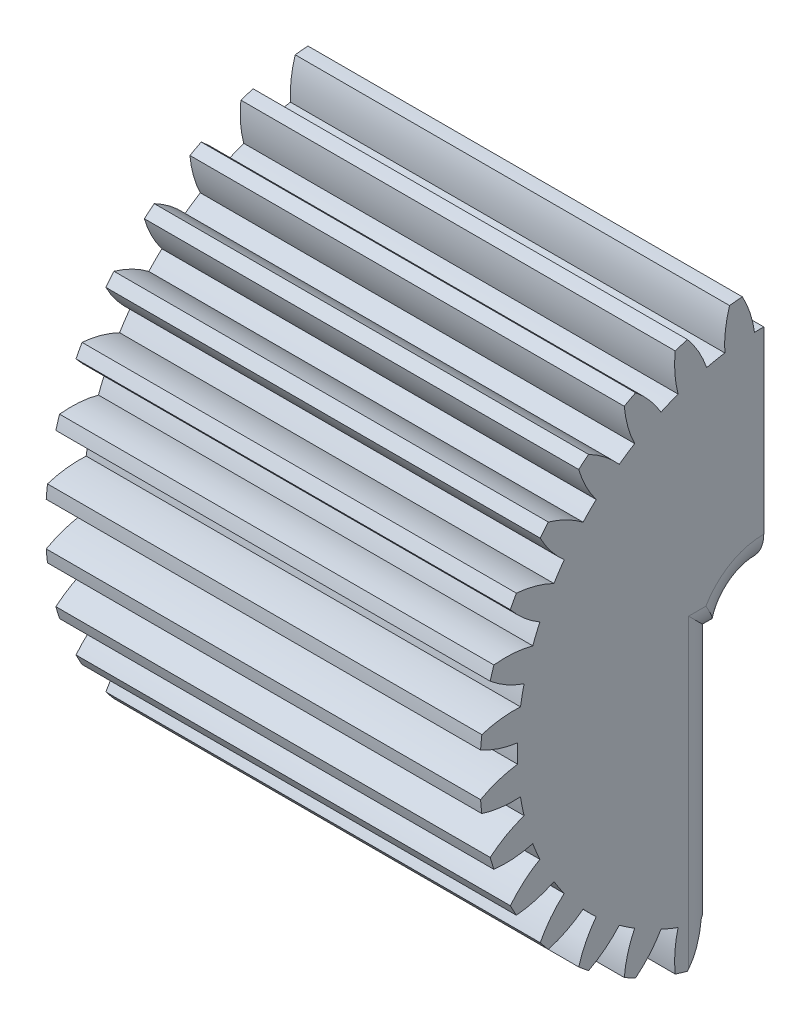
SolidWorks part; units mm, degrees
ref_plane "Plane1" through (0, 0, 0) normal (0, 0, 1) x (1, 0, 0)
ref_plane "Plane2" through (0, 0, 0) normal (0, 1, 0) x (1, 0, 0)
ref_plane "Plane3" through (0, 0, 0) normal (1, 0, 0) x (0, 0, -1)
other "Configuration Table"
sketch "HoldingSke" plane through (0, 0, 0) normal (0, 1, 0) x (1, 0, 0)
  line L0 (0, 0) -> (1.6961, -1.0598)
  line L1 (-15, 0) -> (100, 0) construction
  line L2 (0, 0) -> (-2.1039, 2.3779)
  line L3 (0, 0) -> (-11.863, 4.5341)
  line L4 (0, 0) -> (7.3237, 4.5764)
  line L5 (0, 0) -> (-46.8476, -17.4728)
  line L6 (0, 0) -> (-8.2896, -5.593)
  line L7 (-2.1039, 2.3779) -> (8.6586, 51.2059)
  line L8 (-76.2, 54.61) -> (-75.9, 54.61)
  line L9 (-67.7845, 28.3722) -> (-49.3413, 33.142)
  line L10 (-76.2, 71.12) -> (104.1128, 71.12)
  line L11 (0, 0) -> (-10, 0)
  line L12 (-76.2, 101.6) -> (-76.181, 101.6)
  line L13 (24.9733, 27.94) -> (52.9518, 28.4284)
  line L14 (24.9733, 27.94) -> (24.9743, 27.94)
  line L15 (24.9733, 27.94) -> (100.4006, 29.5858)
  line L16 (-63.627, -0.5) -> (-12.827, -0.5)
  circle A0 centre (0, 0) radius 1
  circle A1 centre (0, 0) radius 7.374
  circle A2 centre (0, 0) radius 37.5
  circle A3 centre (0, 0) radius 1
  dimension "Num_teeth" = 32
  dimension "Pitch_radius" = 180.3128
  dimension "Width" = 10
  dimension "Thickness" = 10
sketch "BasProSke" plane through (0, 0, 0) normal (0, 1, 0) x (1, 0, 0)
  line L0 (-10, 0) -> (60, 0) construction
  line L1 (0, 0) -> (0, 8.5)
  line L2 (0, 0) -> (10, 0)
  line L3 (10, 0) -> (10, 8.5)
  line L4 (10, 8.5) -> (0, 8.5)
  dimension "Thickness" = 10
  dimension "Diameter" = 17
revolve "Base-Revolve" add sketch "BasProSke" angle 360 about L0
sketch "TooCutSke" plane through (0, 0, 0) normal (1, 0, 0) x (0, 0, -1)
  line L1 (0, 0) -> (0, 107) construction
  line L2 (0, 0) -> (-0.4258, 7.9887) construction
  line L3 (0, 0) -> (-1.5667, 15.9069) construction
  line L4 (-0.4258, 7.9887) -> (-0.7833, 7.9534) construction
  arc A0 (0.277, 7.3688) -> (-0.277, 7.3688) centre (0, 0) ccw
  arc A1 (0.6561, 8.5001) -> (-0.6561, 8.5001) centre (0, 0) ccw
  circle A2 centre (0, 0) radius 8 construction
  circle A3 centre (0, 0) radius 7.7452 construction
  arc A4 (-0.277, 7.3688) -> (-0.6561, 8.5001) centre (-3.4475, 6.9356) ccw
  arc A5 (0.6561, 8.5001) -> (0.277, 7.3688) centre (3.4475, 6.9356) ccw
extrude "ToothCut" cut sketch "TooCutSke" along normal through all
fillet "Breaks" [suppressed] radius 0.01 tangent propagation no
fillet "RootFillets" [suppressed] radius 0.126
pattern_circular "TeethCuts" count 32 every 11.25 about axis through (-10, 0, 0) along (1, 0, 0) of "ToothCut", "RootFillets", "Breaks"
sketch "HubNeaOneSke" plane through (0, 0, 0) normal (-1, 0, 0) x (0, 0, 1)
  circle A0 centre (0, 0) radius 7.374
  dimension "Diameter" = 14.748
extrude "HubNearOne" [suppressed] add sketch "HubNeaOneSke" along normal blind 40.0001
sketch "HubNeaBotSke" plane through (0, 0, 0) normal (-1, 0, 0) x (0, 0, 1)
  circle A0 centre (0, 0) radius 7.374
  dimension "Diameter" = 14.748
extrude "HubNearBoth" [suppressed] add sketch "HubNeaBotSke" along normal blind 20
ref_plane "FarPln" through (10, 0, 0) normal (1, 0, 0) x (0, 0, -1)
sketch "HubFarSke" plane through (10, 0, 0) normal (1, 0, 0) x (0, 0, -1)
  circle A0 centre (0, 0) radius 7.374
  dimension "Diameter" = 14.748
extrude "HubFar" [suppressed] add sketch "HubFarSke" along normal blind 20
sketch "BorSke" plane through (0, 0, 0) normal (1, 0, 0) x (0, 0, -1)
  circle A0 centre (0, 0) radius 1
  dimension "Diameter" = 2
extrude "Bore" cut sketch "BorSke" along normal mid plane 100.0001
sketch "KeySke" plane through (0, 0, 0) normal (1, 0, 0) x (0, 0, -1)
  line L0 (-0.4, 0) -> (-0.4, 1.3)
  line L1 (-0.4, 1.3) -> (0.4, 1.3)
  line L2 (0.4, 1.3) -> (0.4, 0)
  line L3 (0, 0) -> (0, 34) construction
  line L4 (-0.4, 0) -> (0.4, 0)
  dimension "Width" = 0.8
extrude "Keyway" [suppressed] cut sketch "KeySke" along normal mid plane 100.0001
pattern_circular "Keyway2" [suppressed] count 2 every 90 about axis through (-10, 0, 0) along (1, 0, 0) reverse direction yes
sketch "Sketch1" plane through (10, 0, 0) normal (1, 0, 0) x (0, 0, -1)
  line L1 (-1.1, 0) -> (1.1, 0)
  line L2 (-1.1, 0) -> (-1.1, -12)
  line L3 (-1.1, -12) -> (1.1, -12)
  line L4 (1.1, 0) -> (1.1, -12)
  circle A0 centre (0, 0) radius 1 construction
  dimension "D3" = 12
  dimension "D1" = 2.2
  dimension "D2" = 1.1
  dimension "D4" = 12
extrude "Cut-Extrude1" cut sketch "Sketch1" against normal through all
sketch "Sketch2" plane through (0, 0, 0) normal (0, 0, 1) x (1, 0, 0)
  line L3 (4.25, 0) -> (9.75, 0)
  arc A0 (9.75, 0) -> (4.25, 0) centre (7, 0) ccw
  dimension "D2" = 5.5
  dimension "D1" = 7
revolve "Cut-Revolve1" cut sketch "Sketch2" angle 360 about L3
ref_plane "Plane4" through (3, 0, 0) normal (-1, 0, 0) x (0, 0, 1)
sketch "Sketch4" plane through (3, 0, 0) normal (-1, 0, 0) x (0, 0, 1)
  circle A0 centre (0, 0) radius 1.125
  circle A1 centre (0, 0) radius 0.5
  dimension "D1" = 1
  dimension "D2" = 2.25
extrude "Boss-Extrude1" add sketch "Sketch4" along normal blind 0.5 and the other way blind 0.5
sketch "Sketch5" plane through (0, 0, -1.1) normal (0, 0, 1) x (1, 0, 0)
  line L0 (0, -8.1488) -> (10, -8.1488) construction
  line L1 (0, 0) -> (2.5, 0)
  line L2 (0, 0) -> (0, -8.1488)
  line L3 (0, -8.1488) -> (2.5, -8.1488)
  line L4 (2.5, 0) -> (2.5, -8.1488)
  dimension "D1" = 2.5
extrude "Boss-Extrude2" add sketch "Sketch5" along normal up to next
sketch "Sketch6" plane through (0, 0, 0) normal (-1, 0, 0) x (0, 0, 1)
  line L0 (1, 0) -> (-1, 0) construction
  circle A0 centre (0, 0) radius 2.25
  dimension "D1" = 4.5
extrude "Cut-Extrude4" cut sketch "Sketch6" against normal blind 2.45
sketch "Sketch7" plane through (2.5, 0, 0) normal (1, 0, 0) x (0, 0, -1)
  circle A0 centre (0, 0) radius 0.5
extrude "Cut-Extrude5" cut sketch "Sketch7" against normal blind 2.4
sketch "Sketch8" plane through (0, 0, 0) normal (0, 0, 1) x (1, 0, 0)
  line L0 (0, 0.277) -> (0, -0.277) construction
  line L1 (-0.5, 9) -> (10.5, 9)
  line L2 (-0.5, 9) -> (-0.5, -9)
  line L3 (-0.5, -9) -> (10.5, -9)
  line L4 (10.5, 9) -> (10.5, -9)
  point P6 (0, 0)
  dimension "D1" = 11
  dimension "D2" = 18
  dimension "D3" = 0.5
  dimension "D4" = 9
extrude "Cut-Extrude6" cut sketch "Sketch8" against normal blind 10
sketch "Sketch9" plane through (0, 0, 0) normal (0, 0, -1) x (-1, 0, 0)
  line L0 (-10, 1) -> (-10, 7.374) construction
  line L1 (-8.5, 5.75) -> (-6.5, 5.75)
  line L2 (-8.5, 5.75) -> (-8.5, 3.75)
  line L3 (-8.5, 3.75) -> (-6.5, 3.75)
  line L4 (-6.5, 5.75) -> (-6.5, 3.75)
  line L5 (-3.5, 5.75) -> (-1.5, 5.75)
  line L6 (-3.5, 5.75) -> (-3.5, 3.75)
  line L7 (-3.5, 3.75) -> (-1.5, 3.75)
  line L8 (-1.5, 5.75) -> (-1.5, 3.75)
  line L9 (0, -2.25) -> (0, 2.25) construction
  line L10 (0, 7.374) -> (0, 2.25) construction
  point P12 (0, 0)
  dimension "D1" = 2
  dimension "D2" = 2
  dimension "D3" = 2
  dimension "D4" = 2
  dimension "D5" = 1.5
  dimension "D6" = 3.75
  dimension "D7" = 3.75
  dimension "D8" = 1.5
extrude "Boss-Extrude3" add sketch "Sketch9" along normal blind 2
sketch "Sketch10" plane through (10, 0, 0) normal (1, 0, 0) x (0, 0, -1)
  line L1 (0, 0) -> (-1.25, 0)
  line L2 (0, 0) -> (0, -9)
  line L3 (0, -9) -> (-1.25, -9)
  line L4 (-1.25, 0) -> (-1.25, -9)
  dimension "D1" = 1.25
  dimension "D2" = 9
extrude "Cut-Extrude7" cut sketch "Sketch10" against normal blind 7
ref_plane "Plane5" through (12, 0, 0) normal (1, 0, 0) x (0, 0, -1)
sketch "Sketch11" plane through (12, 0, 0) normal (1, 0, 0) x (0, 0, -1)
  line L0 (-1.25, 0) -> (-1.25, -7.2673) construction
  line L1 (-1, 0) -> (-1.25, 0) construction
  line L2 (0, 1) -> (0, 7.374) construction
  line L3 (-1.25, 0) -> (-1.25, -7.2673)
  line L4 (-1, 0) -> (-1.25, 0)
  line L5 (0, 1) -> (0, 7.374)
  arc A0 (-2.2837, 8.1875) -> (-2.6499, 8.0764) centre (0, 0) ccw construction
  arc A1 (-0.6425, 8.4757) -> (-1.0233, 8.4382) centre (0, 0) ccw construction
  arc A2 (-1.1659, 7.2812) -> (-1.7093, 7.1732) centre (0, 0) ccw construction
  arc A3 (-3.8371, 7.5846) -> (-4.1746, 7.4042) centre (0, 0) ccw construction
  arc A4 (-2.564, 6.9139) -> (-3.0758, 6.7019) centre (0, 0) ccw construction
  arc A5 (-3.8636, 6.2808) -> (-4.3242, 5.973) centre (0, 0) ccw construction
  arc A6 (-5.2431, 6.6903) -> (-5.5389, 6.4475) centre (0, 0) ccw construction
  arc A7 (-5.0147, 5.4064) -> (-5.4064, 5.0147) centre (0, 0) ccw construction
  arc A8 (-6.4475, 5.5389) -> (-6.6903, 5.2431) centre (0, 0) ccw construction
  arc A9 (-7.4042, 4.1746) -> (-7.5846, 3.8371) centre (0, 0) ccw construction
  arc A10 (-5.973, 4.3242) -> (-6.2808, 3.8636) centre (0, 0) ccw construction
  arc A11 (-6.7019, 3.0758) -> (-6.9139, 2.564) centre (0, 0) ccw construction
  arc A12 (-8.0764, 2.6499) -> (-8.1875, 2.2837) centre (0, 0) ccw construction
  arc A13 (-7.1732, 1.7093) -> (-7.2812, 1.1659) centre (0, 0) ccw construction
  arc A14 (-8.4382, 1.0233) -> (-8.4757, 0.6425) centre (0, 0) ccw construction
  arc A15 (-7.3688, 0.277) -> (-7.3688, -0.277) centre (0, 0) ccw construction
  arc A16 (-8.4757, -0.6425) -> (-8.4382, -1.0233) centre (0, 0) ccw construction
  arc A17 (-7.2812, -1.1659) -> (-7.1732, -1.7093) centre (0, 0) ccw construction
  arc A18 (-8.1875, -2.2837) -> (-8.0764, -2.6499) centre (0, 0) ccw construction
  arc A19 (-6.9139, -2.564) -> (-6.7019, -3.0758) centre (0, 0) ccw construction
  arc A20 (-7.5846, -3.8371) -> (-7.4042, -4.1746) centre (0, 0) ccw construction
  arc A21 (-6.2808, -3.8636) -> (-5.973, -4.3242) centre (0, 0) ccw construction
  arc A22 (-6.6903, -5.2431) -> (-6.4475, -5.5389) centre (0, 0) ccw construction
  arc A23 (-5.4064, -5.0147) -> (-5.0147, -5.4064) centre (0, 0) ccw construction
  arc A24 (-5.5389, -6.4475) -> (-5.2431, -6.6903) centre (0, 0) ccw construction
  arc A25 (-4.3242, -5.973) -> (-3.8636, -6.2808) centre (0, 0) ccw construction
  arc A26 (-4.1746, -7.4042) -> (-3.8371, -7.5846) centre (0, 0) ccw construction
  arc A27 (-3.0758, -6.7019) -> (-2.564, -6.9139) centre (0, 0) ccw construction
  arc A28 (-1.7093, -7.1732) -> (-1.25, -7.2673) centre (0, 0) ccw construction
  arc A29 (-2.6499, -8.0764) -> (-2.2837, -8.1875) centre (0, 0) ccw construction
  arc A30 (-2.2837, -8.1875) -> (-1.7093, -7.1732) centre (-4.7344, -6.1297) ccw construction
  arc A31 (-2.564, -6.9139) -> (-2.6499, -8.0764) centre (0.531, -7.727) ccw construction
  arc A32 (-3.8371, -7.5846) -> (-3.0758, -6.7019) centre (-5.8392, -5.0883) ccw construction
  arc A33 (-3.8636, -6.2808) -> (-4.1746, -7.4042) centre (-0.9867, -7.6821) ccw construction
  arc A34 (-5.2431, -6.6903) -> (-4.3242, -5.973) centre (-6.7197, -3.8514) ccw construction
  arc A35 (-5.0147, -5.4064) -> (-5.5389, -6.4475) centre (-2.4664, -7.342) ccw construction
  arc A36 (-6.4475, -5.5389) -> (-5.4064, -5.0147) centre (-7.342, -2.4664) ccw construction
  arc A37 (-5.973, -4.3242) -> (-6.6903, -5.2431) centre (-3.8514, -6.7197) ccw construction
  arc A38 (-7.4042, -4.1746) -> (-6.2808, -3.8636) centre (-7.6821, -0.9867) ccw construction
  arc A39 (-6.7019, -3.0758) -> (-7.5846, -3.8371) centre (-5.0883, -5.8392) ccw construction
  arc A40 (-8.0764, -2.6499) -> (-6.9139, -2.564) centre (-7.727, 0.531) ccw construction
  arc A41 (-7.1732, -1.7093) -> (-8.1875, -2.2837) centre (-6.1297, -4.7344) ccw construction
  arc A42 (-8.4382, -1.0233) -> (-7.2812, -1.1659) centre (-7.4749, 2.0282) ccw construction
  arc A43 (-7.3688, -0.277) -> (-8.4757, -0.6425) centre (-6.9356, -3.4475) ccw construction
  arc A44 (-8.4757, 0.6425) -> (-7.3688, 0.277) centre (-6.9356, 3.4475) ccw construction
  arc A45 (-7.2812, 1.1659) -> (-8.4382, 1.0233) centre (-7.4749, -2.0282) ccw construction
  arc A46 (-8.1875, 2.2837) -> (-7.1732, 1.7093) centre (-6.1297, 4.7344) ccw construction
  arc A47 (-6.9139, 2.564) -> (-8.0764, 2.6499) centre (-7.727, -0.531) ccw construction
  arc A48 (-7.5846, 3.8371) -> (-6.7019, 3.0758) centre (-5.0883, 5.8392) ccw construction
  arc A49 (-6.2808, 3.8636) -> (-7.4042, 4.1746) centre (-7.6821, 0.9867) ccw construction
  arc A50 (-6.6903, 5.2431) -> (-5.973, 4.3242) centre (-3.8514, 6.7197) ccw construction
  arc A51 (-5.4064, 5.0147) -> (-6.4475, 5.5389) centre (-7.342, 2.4664) ccw construction
  arc A52 (-5.5389, 6.4475) -> (-5.0147, 5.4064) centre (-2.4664, 7.342) ccw construction
  arc A53 (-4.3242, 5.973) -> (-5.2431, 6.6903) centre (-6.7197, 3.8514) ccw construction
  arc A54 (-4.1746, 7.4042) -> (-3.8636, 6.2808) centre (-0.9867, 7.6821) ccw construction
  arc A55 (-3.0758, 6.7019) -> (-3.8371, 7.5846) centre (-5.8392, 5.0883) ccw construction
  arc A56 (-2.6499, 8.0764) -> (-2.564, 6.9139) centre (0.531, 7.727) ccw construction
  arc A57 (-1.7093, 7.1732) -> (-2.2837, 8.1875) centre (-4.7344, 6.1297) ccw construction
  arc A58 (-1.0233, 8.4382) -> (-1.1659, 7.2812) centre (2.0282, 7.4749) ccw construction
  arc A59 (-0.277, 7.3688) -> (-0.6425, 8.4757) centre (-3.4475, 6.9356) ccw construction
  arc A60 (0, 7.374) -> (-0.277, 7.3688) centre (0, 0) ccw construction
  arc A61 (0, 1) -> (-1, 0) centre (0, 0) ccw construction
  arc A62 (-2.2837, 8.1875) -> (-2.6499, 8.0764) centre (0, 0) ccw
  arc A63 (-0.6425, 8.4757) -> (-1.0233, 8.4382) centre (0, 0) ccw
  arc A64 (-1.1659, 7.2812) -> (-1.7093, 7.1732) centre (0, 0) ccw
  arc A65 (-3.8371, 7.5846) -> (-4.1746, 7.4042) centre (0, 0) ccw
  arc A66 (-2.564, 6.9139) -> (-3.0758, 6.7019) centre (0, 0) ccw
  arc A67 (-3.8636, 6.2808) -> (-4.3242, 5.973) centre (0, 0) ccw
  arc A68 (-5.2431, 6.6903) -> (-5.5389, 6.4475) centre (0, 0) ccw
  arc A69 (-5.0147, 5.4064) -> (-5.4064, 5.0147) centre (0, 0) ccw
  arc A70 (-6.4475, 5.5389) -> (-6.6903, 5.2431) centre (0, 0) ccw
  arc A71 (-7.4042, 4.1746) -> (-7.5846, 3.8371) centre (0, 0) ccw
  arc A72 (-5.973, 4.3242) -> (-6.2808, 3.8636) centre (0, 0) ccw
  arc A73 (-6.7019, 3.0758) -> (-6.9139, 2.564) centre (0, 0) ccw
  arc A74 (-8.0764, 2.6499) -> (-8.1875, 2.2837) centre (0, 0) ccw
  arc A75 (-7.1732, 1.7093) -> (-7.2812, 1.1659) centre (0, 0) ccw
  arc A76 (-8.4382, 1.0233) -> (-8.4757, 0.6425) centre (0, 0) ccw
  arc A77 (-7.3688, 0.277) -> (-7.3688, -0.277) centre (0, 0) ccw
  arc A78 (-8.4757, -0.6425) -> (-8.4382, -1.0233) centre (0, 0) ccw
  arc A79 (-7.2812, -1.1659) -> (-7.1732, -1.7093) centre (0, 0) ccw
  arc A80 (-8.1875, -2.2837) -> (-8.0764, -2.6499) centre (0, 0) ccw
  arc A81 (-6.9139, -2.564) -> (-6.7019, -3.0758) centre (0, 0) ccw
  arc A82 (-7.5846, -3.8371) -> (-7.4042, -4.1746) centre (0, 0) ccw
  arc A83 (-6.2808, -3.8636) -> (-5.973, -4.3242) centre (0, 0) ccw
  arc A84 (-6.6903, -5.2431) -> (-6.4475, -5.5389) centre (0, 0) ccw
  arc A85 (-5.4064, -5.0147) -> (-5.0147, -5.4064) centre (0, 0) ccw
  arc A86 (-5.5389, -6.4475) -> (-5.2431, -6.6903) centre (0, 0) ccw
  arc A87 (-4.3242, -5.973) -> (-3.8636, -6.2808) centre (0, 0) ccw
  arc A88 (-4.1746, -7.4042) -> (-3.8371, -7.5846) centre (0, 0) ccw
  arc A89 (-3.0758, -6.7019) -> (-2.564, -6.9139) centre (0, 0) ccw
  arc A90 (-1.7093, -7.1732) -> (-1.25, -7.2673) centre (0, 0) ccw
  arc A91 (-2.6499, -8.0764) -> (-2.2837, -8.1875) centre (0, 0) ccw
  arc A92 (-2.2837, -8.1875) -> (-1.7093, -7.1732) centre (-4.7344, -6.1297) ccw
  arc A93 (-2.564, -6.9139) -> (-2.6499, -8.0764) centre (0.531, -7.727) ccw
  arc A94 (-3.8371, -7.5846) -> (-3.0758, -6.7019) centre (-5.8392, -5.0883) ccw
  arc A95 (-3.8636, -6.2808) -> (-4.1746, -7.4042) centre (-0.9867, -7.6821) ccw
  arc A96 (-5.2431, -6.6903) -> (-4.3242, -5.973) centre (-6.7197, -3.8514) ccw
  arc A97 (-5.0147, -5.4064) -> (-5.5389, -6.4475) centre (-2.4664, -7.342) ccw
  arc A98 (-6.4475, -5.5389) -> (-5.4064, -5.0147) centre (-7.342, -2.4664) ccw
  arc A99 (-5.973, -4.3242) -> (-6.6903, -5.2431) centre (-3.8514, -6.7197) ccw
  arc A100 (-7.4042, -4.1746) -> (-6.2808, -3.8636) centre (-7.6821, -0.9867) ccw
  arc A101 (-6.7019, -3.0758) -> (-7.5846, -3.8371) centre (-5.0883, -5.8392) ccw
  arc A102 (-8.0764, -2.6499) -> (-6.9139, -2.564) centre (-7.727, 0.531) ccw
  arc A103 (-7.1732, -1.7093) -> (-8.1875, -2.2837) centre (-6.1297, -4.7344) ccw
  arc A104 (-8.4382, -1.0233) -> (-7.2812, -1.1659) centre (-7.4749, 2.0282) ccw
  arc A105 (-7.3688, -0.277) -> (-8.4757, -0.6425) centre (-6.9356, -3.4475) ccw
  arc A106 (-8.4757, 0.6425) -> (-7.3688, 0.277) centre (-6.9356, 3.4475) ccw
  arc A107 (-7.2812, 1.1659) -> (-8.4382, 1.0233) centre (-7.4749, -2.0282) ccw
  arc A108 (-8.1875, 2.2837) -> (-7.1732, 1.7093) centre (-6.1297, 4.7344) ccw
  arc A109 (-6.9139, 2.564) -> (-8.0764, 2.6499) centre (-7.727, -0.531) ccw
  arc A110 (-7.5846, 3.8371) -> (-6.7019, 3.0758) centre (-5.0883, 5.8392) ccw
  arc A111 (-6.2808, 3.8636) -> (-7.4042, 4.1746) centre (-7.6821, 0.9867) ccw
  arc A112 (-6.6903, 5.2431) -> (-5.973, 4.3242) centre (-3.8514, 6.7197) ccw
  arc A113 (-5.4064, 5.0147) -> (-6.4475, 5.5389) centre (-7.342, 2.4664) ccw
  arc A114 (-5.5389, 6.4475) -> (-5.0147, 5.4064) centre (-2.4664, 7.342) ccw
  arc A115 (-4.3242, 5.973) -> (-5.2431, 6.6903) centre (-6.7197, 3.8514) ccw
  arc A116 (-4.1746, 7.4042) -> (-3.8636, 6.2808) centre (-0.9867, 7.6821) ccw
  arc A117 (-3.0758, 6.7019) -> (-3.8371, 7.5846) centre (-5.8392, 5.0883) ccw
  arc A118 (-2.6499, 8.0764) -> (-2.564, 6.9139) centre (0.531, 7.727) ccw
  arc A119 (-1.7093, 7.1732) -> (-2.2837, 8.1875) centre (-4.7344, 6.1297) ccw
  arc A120 (-1.0233, 8.4382) -> (-1.1659, 7.2812) centre (2.0282, 7.4749) ccw
  arc A121 (-0.277, 7.3688) -> (-0.6425, 8.4757) centre (-3.4475, 6.9356) ccw
  arc A122 (0, 7.374) -> (-0.277, 7.3688) centre (0, 0) ccw
  arc A123 (0, 1) -> (-1, 0) centre (0, 0) ccw
extrude "Boss-Extrude4" add sketch "Sketch11" against normal up to next
sketch "Sketch12" plane through (2.45, 0, 0) normal (-1, 0, 0) x (0, 0, 1)
  circle A0 centre (0, 0) radius 0.5
  circle A1 centre (0, 0) radius 1.125
  dimension "D1" = 2.25
  dimension "D2" = 1
extrude "Boss-Extrude5" add sketch "Sketch12" against normal blind 1
sketch "Sketch13" plane through (0, 0, 0) normal (0, 0, -1) x (-1, 0, 0)
  line L1 (-3.658, 2.1069) -> (-1.958, 2.1069)
  line L2 (-3.658, 2.1069) -> (-3.658, -1.8931)
  line L3 (-3.658, -1.8931) -> (-1.958, -1.8931)
  line L4 (-1.958, 2.1069) -> (-1.958, -1.8931)
  dimension "D1" = 1.7
  dimension "D2" = 4
extrude "Cut-Extrude8" cut sketch "Sketch13" along normal through all
ref_plane "Plane6" through (13, 0, 0) normal (1, 0, 0) x (0, 0, -1)
sketch "Sketch14" plane through (13, 0, 0) normal (1, 0, 0) x (0, 0, -1)
  line L3 (-1.25, 0) -> (-1.25, -7.2673)
  line L4 (-1, 0) -> (-1.25, 0)
  line L5 (0, 1) -> (0, 7.374)
  arc A62 (-2.2837, 8.1875) -> (-2.6499, 8.0764) centre (0, 0) ccw
  arc A63 (-0.6425, 8.4757) -> (-1.0233, 8.4382) centre (0, 0) ccw
  arc A64 (-1.1659, 7.2812) -> (-1.7093, 7.1732) centre (0, 0) ccw
  arc A65 (-3.8371, 7.5846) -> (-4.1746, 7.4042) centre (0, 0) ccw
  arc A66 (-2.564, 6.9139) -> (-3.0758, 6.7019) centre (0, 0) ccw
  arc A67 (-3.8636, 6.2808) -> (-4.3242, 5.973) centre (0, 0) ccw
  arc A68 (-5.2431, 6.6903) -> (-5.5389, 6.4475) centre (0, 0) ccw
  arc A69 (-5.0147, 5.4064) -> (-5.4064, 5.0147) centre (0, 0) ccw
  arc A70 (-6.4475, 5.5389) -> (-6.6903, 5.2431) centre (0, 0) ccw
  arc A71 (-7.4042, 4.1746) -> (-7.5846, 3.8371) centre (0, 0) ccw
  arc A72 (-5.973, 4.3242) -> (-6.2808, 3.8636) centre (0, 0) ccw
  arc A73 (-6.7019, 3.0758) -> (-6.9139, 2.564) centre (0, 0) ccw
  arc A74 (-8.0764, 2.6499) -> (-8.1875, 2.2837) centre (0, 0) ccw
  arc A75 (-7.1732, 1.7093) -> (-7.2812, 1.1659) centre (0, 0) ccw
  arc A76 (-8.4382, 1.0233) -> (-8.4757, 0.6425) centre (0, 0) ccw
  arc A77 (-7.3688, 0.277) -> (-7.3688, -0.277) centre (0, 0) ccw
  arc A78 (-8.4757, -0.6425) -> (-8.4382, -1.0233) centre (0, 0) ccw
  arc A79 (-7.2812, -1.1659) -> (-7.1732, -1.7093) centre (0, 0) ccw
  arc A80 (-8.1875, -2.2837) -> (-8.0764, -2.6499) centre (0, 0) ccw
  arc A81 (-6.9139, -2.564) -> (-6.7019, -3.0758) centre (0, 0) ccw
  arc A82 (-7.5846, -3.8371) -> (-7.4042, -4.1746) centre (0, 0) ccw
  arc A83 (-6.2808, -3.8636) -> (-5.973, -4.3242) centre (0, 0) ccw
  arc A84 (-6.6903, -5.2431) -> (-6.4475, -5.5389) centre (0, 0) ccw
  arc A85 (-5.4064, -5.0147) -> (-5.0147, -5.4064) centre (0, 0) ccw
  arc A86 (-5.5389, -6.4475) -> (-5.2431, -6.6903) centre (0, 0) ccw
  arc A87 (-4.3242, -5.973) -> (-3.8636, -6.2808) centre (0, 0) ccw
  arc A88 (-4.1746, -7.4042) -> (-3.8371, -7.5846) centre (0, 0) ccw
  arc A89 (-3.0758, -6.7019) -> (-2.564, -6.9139) centre (0, 0) ccw
  arc A90 (-1.7093, -7.1732) -> (-1.25, -7.2673) centre (0, 0) ccw
  arc A91 (-2.6499, -8.0764) -> (-2.2837, -8.1875) centre (0, 0) ccw
  arc A92 (-2.2837, -8.1875) -> (-1.7093, -7.1732) centre (-4.7344, -6.1297) ccw
  arc A93 (-2.564, -6.9139) -> (-2.6499, -8.0764) centre (0.531, -7.727) ccw
  arc A94 (-3.8371, -7.5846) -> (-3.0758, -6.7019) centre (-5.8392, -5.0883) ccw
  arc A95 (-3.8636, -6.2808) -> (-4.1746, -7.4042) centre (-0.9867, -7.6821) ccw
  arc A96 (-5.2431, -6.6903) -> (-4.3242, -5.973) centre (-6.7197, -3.8514) ccw
  arc A97 (-5.0147, -5.4064) -> (-5.5389, -6.4475) centre (-2.4664, -7.342) ccw
  arc A98 (-6.4475, -5.5389) -> (-5.4064, -5.0147) centre (-7.342, -2.4664) ccw
  arc A99 (-5.973, -4.3242) -> (-6.6903, -5.2431) centre (-3.8514, -6.7197) ccw
  arc A100 (-7.4042, -4.1746) -> (-6.2808, -3.8636) centre (-7.6821, -0.9867) ccw
  arc A101 (-6.7019, -3.0758) -> (-7.5846, -3.8371) centre (-5.0883, -5.8392) ccw
  arc A102 (-8.0764, -2.6499) -> (-6.9139, -2.564) centre (-7.727, 0.531) ccw
  arc A103 (-7.1732, -1.7093) -> (-8.1875, -2.2837) centre (-6.1297, -4.7344) ccw
  arc A104 (-8.4382, -1.0233) -> (-7.2812, -1.1659) centre (-7.4749, 2.0282) ccw
  arc A105 (-7.3688, -0.277) -> (-8.4757, -0.6425) centre (-6.9356, -3.4475) ccw
  arc A106 (-8.4757, 0.6425) -> (-7.3688, 0.277) centre (-6.9356, 3.4475) ccw
  arc A107 (-7.2812, 1.1659) -> (-8.4382, 1.0233) centre (-7.4749, -2.0282) ccw
  arc A108 (-8.1875, 2.2837) -> (-7.1732, 1.7093) centre (-6.1297, 4.7344) ccw
  arc A109 (-6.9139, 2.564) -> (-8.0764, 2.6499) centre (-7.727, -0.531) ccw
  arc A110 (-7.5846, 3.8371) -> (-6.7019, 3.0758) centre (-5.0883, 5.8392) ccw
  arc A111 (-6.2808, 3.8636) -> (-7.4042, 4.1746) centre (-7.6821, 0.9867) ccw
  arc A112 (-6.6903, 5.2431) -> (-5.973, 4.3242) centre (-3.8514, 6.7197) ccw
  arc A113 (-5.4064, 5.0147) -> (-6.4475, 5.5389) centre (-7.342, 2.4664) ccw
  arc A114 (-5.5389, 6.4475) -> (-5.0147, 5.4064) centre (-2.4664, 7.342) ccw
  arc A115 (-4.3242, 5.973) -> (-5.2431, 6.6903) centre (-6.7197, 3.8514) ccw
  arc A116 (-4.1746, 7.4042) -> (-3.8636, 6.2808) centre (-0.9867, 7.6821) ccw
  arc A117 (-3.0758, 6.7019) -> (-3.8371, 7.5846) centre (-5.8392, 5.0883) ccw
  arc A118 (-2.6499, 8.0764) -> (-2.564, 6.9139) centre (0.531, 7.727) ccw
  arc A119 (-1.7093, 7.1732) -> (-2.2837, 8.1875) centre (-4.7344, 6.1297) ccw
  arc A120 (-1.0233, 8.4382) -> (-1.1659, 7.2812) centre (2.0282, 7.4749) ccw
  arc A121 (-0.277, 7.3688) -> (-0.6425, 8.4757) centre (-3.4475, 6.9356) ccw
  arc A122 (0, 7.374) -> (-0.277, 7.3688) centre (0, 0) ccw
  arc A123 (0, 1) -> (-1, 0) centre (0, 0) ccw
extrude "Boss-Extrude6" add sketch "Sketch14" against normal blind 1.25
fillet "Fillet1" radius 1 3 edges at (13, 0, 1.125) (13, 0.7071, 0.7071) (13, -3.6336, 1.25)
equation "' \"Module@HoldingSke\" = 6.35"
equation "' \"Num_teeth@HoldingSke\" = 12"
equation "' \"Ap@HoldingSke\" =  20"
equation "' \"Ap@HoldingSke\" = 20"
equation "' \"Width@HoldingSke\" = 0.5 * 25.4"
equation "' \"Hub_dia@HoldingSke\"= 1 * 25.4"
equation "' \"Hub_dia@HoldingSke\" = 1 * 25.4"
equation "' \"Overall_len@HoldingSke\" = 1.0 * 25.4"
equation "' \"Bore@HoldingSke\" = 0.75 * 25.4"
equation "' \"T_dim@HoldingSke\" = 0.1 * 25.4"
equation "' \"Width@KeySke\" = 0.25 * 25.4"
equation "' \"Show_teeth@HoldingSke\" = 13"
equation "' \"Backlash@HoldingSke\" = 0.009 * 25.4"
equation "' \"Addendum_fac@HoldingSke\" = 1.0"
equation "' \"Dedendum_fac@HoldingSke\" = 1.25"
equation "' \"Dedendum_add@HoldingSke\" = 0.00005 * 25.4"
equation "' \"Clearance_fac@HoldingSke\" = 0.25"
equation "\"Pitch@HoldingSke\" = 1 / \"Module@HoldingSke\""
equation "\"Overcut_dia@TooCutSke\" = (\"Num_teeth@HoldingSke\" + 2 * \"Addendum_fac@HoldingSke\") / \"Pitch@HoldingSke\" + 0.002 * 25.4"
equation "\"Pitch_dia@TooCutSke\" = \"Num_teeth@HoldingSke\" / \"Pitch@HoldingSke\""
equation "\"Base_dia@TooCutSke\" = \"Num_teeth@HoldingSke\" / \"Pitch@HoldingSke\" * cos((\"Ap@HoldingSke\"  * 3.14159265 / 180))"
equation "\"Root_dia@TooCutSke\" = (\"Num_teeth@HoldingSke\" + 2) / \"Pitch@HoldingSke\" - 2 * (\"Addendum_fac@HoldingSke\" + \"Dedendum_fac@HoldingSke\") / \"Pitch@HoldingSke\" - \"Dedendum_add@HoldingSke\" * 2"
equation "\"Half_ang@TooCutSke\" = 180 / \"Num_teeth@HoldingSke\""
equation "\"Half_CT@TooCutSke\" = \"Num_teeth@HoldingSke\" / \"Pitch@HoldingSke\" * sin((3.14159265 / 2 / \"Num_teeth@HoldingSke\")) / 2 - 7 * \"Backlash@HoldingSke\" / 4"
equation "\"Flank_rad@TooCutSke\" = \"Num_teeth@HoldingSke\" / \"Pitch@HoldingSke\" / 5"
equation "\"Radius@RootFillets\" = \"Clearance_fac@HoldingSke\" / \"Pitch@HoldingSke\" + \"Dedendum_add@HoldingSke\""
equation "\"Break_rad@Breaks\" = 0.02 / \"Pitch@HoldingSke\""
equation "\"Thickness@HoldingSke\" = \"Width@HoldingSke\""
equation "\"OAL@HoldingSke\" = \"Thickness@HoldingSke\""
equation "\"MHD@HoldingSke\" = (\"Num_teeth@HoldingSke\" + 2) / \"Pitch@HoldingSke\" - 2 * (\"Addendum_fac@HoldingSke\" + \"Dedendum_fac@HoldingSke\")  / \"Pitch@HoldingSke\" - \"Dedendum_add@HoldingSke\" * 2"
equation "\"MBD@HoldingSke\" = (\"Num_teeth@HoldingSke\" + 2) / \"Pitch@HoldingSke\" - 2 * (\"Addendum_fac@HoldingSke\" + \"Dedendum_fac@HoldingSke\")  / \"Pitch@HoldingSke\" - \"Dedendum_add@HoldingSke\" * 2 - 0.002 * 25.4"
equation "\"MHD@HoldingSke\" = ((sgn( \"MHD@HoldingSke\" - \"Hub_dia@HoldingSke\" )-1)*( \"MHD@HoldingSke\" - \"Hub_dia@HoldingSke\" ))/-2+ \"Hub_dia@HoldingSke\""
equation "\"MBD@HoldingSke\" = ((sgn( \"MBD@HoldingSke\" - \"Bore@HoldingSke\" )-1)*( \"MBD@HoldingSke\" - \"Bore@HoldingSke\" ))/-2+ \"Bore@HoldingSke\""
equation "\"OAL@HoldingSke\" = ((sgn( \"OAL@HoldingSke\" - \"Overall_len@HoldingSke\" )+1)*( \"OAL@HoldingSke\" - \"Overall_len@HoldingSke\" ))/2 + \"Overall_len@HoldingSke\" + 0.000002 * 25.4"
equation "\"Num_teeth@TeethCuts\" = int( \"Show_teeth@HoldingSke\" ) + 1"
equation "\"Num_teeth@TeethCuts\" = ((sgn( \"Num_teeth@TeethCuts\" - \"Num_teeth@HoldingSke\" )-1)*( \"Num_teeth@TeethCuts\" - \"Num_teeth@HoldingSke\" ))/-2+ \"Num_teeth@HoldingSke\""
equation "\"Num_teeth@TeethCuts\" = ((sgn( \"Num_teeth@TeethCuts\" - 2.0)+1)*( \"Num_teeth@TeethCuts\" - 2.0))/2 +2.0"
equation "\"Angle@TeethCuts\" = 360.0 / \"Num_teeth@HoldingSke\""
equation "\"Diameter@BasProSke\" = (\"Num_teeth@HoldingSke\" + 2 * \"Addendum_fac@HoldingSke\") / \"Pitch@HoldingSke\""
equation "\"Thickness@BasProSke\"  = \"Thickness@HoldingSke\""
equation "' \"Fillet_rad@BasProSke\" =  \"Thickness@HoldingSke\" * 0.05"
equation "' \"Fillet_rad@BasProSke\" = \"Thickness@HoldingSke\" * 0.05"
equation "\"MHD@HoldingSke\" = ((sgn( \"MHD@HoldingSke\" - \"Root_dia@TooCutSke\" )-1)*( \"MHD@HoldingSke\" - \"Root_dia@TooCutSke\" ))/-2+ \"Root_dia@TooCutSke\""
equation "\"Diameter@HubNeaOneSke\" = \"MHD@HoldingSke\""
equation "\"Length@HubNearOne\" = \"OAL@HoldingSke\" - \"Thickness@BasProSke\""
equation "\"Diameter@HubNeaBotSke\" = \"MHD@HoldingSke\""
equation "\"Length@HubNearBoth\" = ( \"OAL@HoldingSke\" - \"Thickness@BasProSke\" ) / 2.0"
equation "\"Thickness@FarPln\" = \"Thickness@BasProSke\""
equation "\"Diameter@HubFarSke\" = \"MHD@HoldingSke\""
equation "\"Length@HubFar\" = ( \"OAL@HoldingSke\" - \"Thickness@BasProSke\" ) / 2.0"
equation "\"Diameter@BorSke\" = \"MBD@HoldingSke\""
equation "\"D1@Bore\" = \"OAL@HoldingSke\" * 2.0"
equation "\"D1@Keyway\" = \"OAL@HoldingSke\" * 2.0"
equation "\"Offset@KeySke\" = \"T_dim@HoldingSke\" + \"MBD@HoldingSke\" / 2.0"
